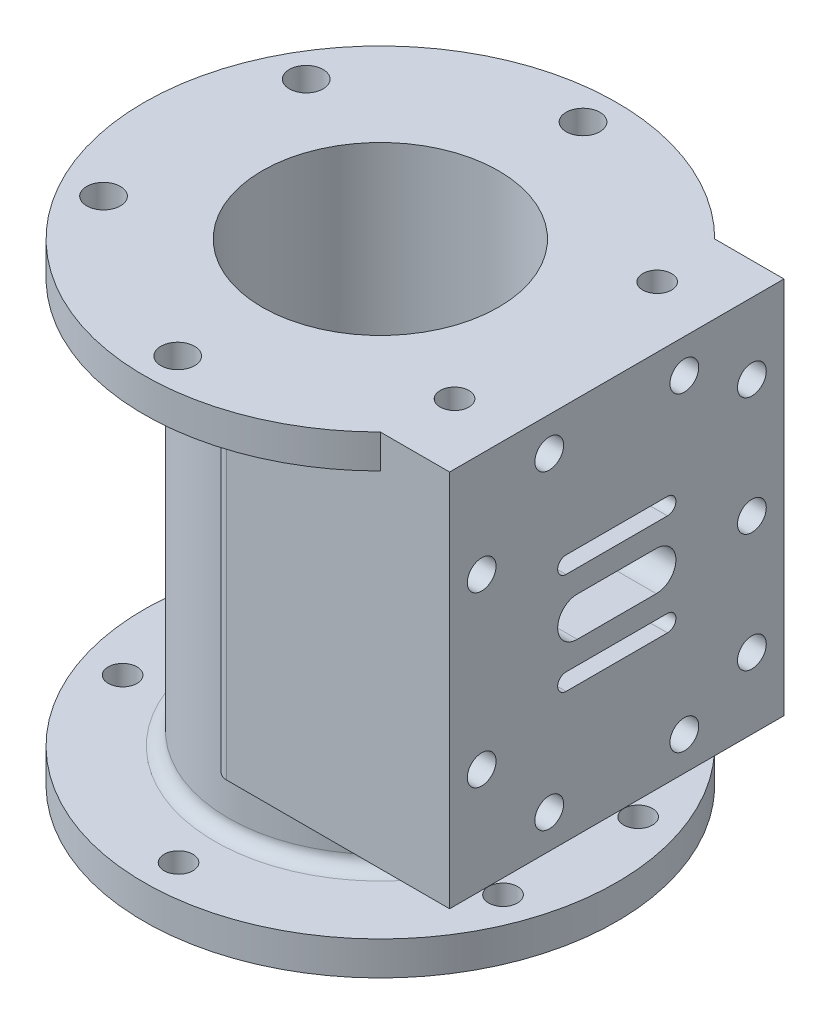
SolidWorks part; units mm, degrees
ref_plane "Front Plane" through (0, 0, 0) normal (0, 0, 1) x (1, 0, 0)
ref_plane "Top Plane" through (0, 0, 0) normal (0, 1, 0) x (1, 0, 0)
ref_plane "Right Plane" through (0, 0, 0) normal (1, 0, 0) x (0, 0, -1)
sketch "Sketch2" plane through (0, 0, 0) normal (0, 0, 1) x (1, 0, 0)
  line L0 (0, -56.0843) -> (0, 32.8157) construction
  line L1 (-22.225, 38.5088) -> (-44.45, 38.5088)
  line L2 (-44.45, 38.5088) -> (-44.45, 32.1588)
  line L3 (-44.45, 32.1588) -> (-28.575, 32.1588)
  line L4 (-28.575, 32.1588) -> (-28.575, -44.0412)
  line L5 (-28.575, -44.0412) -> (-44.45, -44.0412)
  line L6 (-44.45, -44.0412) -> (-44.45, -50.3912)
  line L7 (-44.45, -50.3912) -> (-22.225, -50.3912)
  line L8 (-22.225, -50.3912) -> (-22.225, 26.4657)
  line L9 (-22.225, 26.4657) -> (-22.225, 38.5088)
  dimension "D1" = 88.9
  dimension "D2" = 6.35
  dimension "D3" = 44.45
  dimension "D4" = 57.15
  dimension "D5" = 88.9
  dimension "D6" = 88.9
  dimension "D7" = 6.35
revolve "Revolve1" add sketch "Sketch2" angle 360 about L0
ref_plane "Plane1" through (44.45, 0, 0) normal (1, 0, 0) x (0, 0, -1)
sketch "Sketch3" plane through (44.45, 0, 0) normal (1, 0, 0) x (0, 0, -1)
  line L0 (31.4325, 38.5088) -> (-31.4325, 38.5088)
  line L1 (22.225, 38.5088) -> (-22.225, 38.5088) construction
  line L2 (44.45, 38.5088) -> (-44.45, 38.5088) construction
  line L3 (-31.4325, 38.5088) -> (-31.4325, -32.6112)
  line L4 (-31.4325, -32.6112) -> (31.4325, -32.6112)
  line L5 (0, -32.6112) -> (0, 38.5088) construction
  line L6 (31.4325, 38.5088) -> (31.4325, -32.6112)
  line L7 (-7.4295, 2.9488) -> (7.4295, 2.9488) construction
  line L8 (-7.4295, 6.6318) -> (7.4295, 6.6318)
  line L9 (-7.4295, -0.7342) -> (7.4295, -0.7342)
  line L10 (-9.525, 12.4738) -> (9.525, 12.4738) construction
  line L11 (-9.525, 14.0613) -> (9.525, 14.0613)
  line L12 (-9.525, 10.8863) -> (9.525, 10.8863)
  line L13 (0, 2.9488) -> (27.4597, 2.9488) construction
  line L14 (-9.525, -6.5762) -> (9.525, -6.5762) construction
  line L15 (-9.525, -8.1637) -> (9.525, -8.1637)
  line L16 (-9.525, -4.9887) -> (9.525, -4.9887)
  line L17 (25.4, 25.1738) -> (25.4, -19.2762) construction
  line L18 (-17.7165, 24.7928) -> (17.7165, 24.7928) construction
  line L19 (-17.7165, 24.7928) -> (-17.7165, -18.8952) construction
  line L20 (-17.7165, -18.8952) -> (17.7165, -18.8952) construction
  line L21 (17.7165, 24.7928) -> (17.7165, -18.8952) construction
  line L22 (-17.7165, 24.7928) -> (17.7165, -18.8952) construction
  line L23 (-17.7165, -18.8952) -> (17.7165, 24.7928) construction
  arc A0 (-7.4295, 6.6318) -> (-7.4295, -0.7342) centre (-7.4295, 2.9488) ccw
  arc A1 (7.4295, -0.7342) -> (7.4295, 6.6318) centre (7.4295, 2.9488) ccw
  arc A2 (-9.525, 14.0613) -> (-9.525, 10.8863) centre (-9.525, 12.4738) ccw
  arc A3 (9.525, 10.8863) -> (9.525, 14.0613) centre (9.525, 12.4738) ccw
  arc A4 (-9.525, -8.1637) -> (-9.525, -4.9887) centre (-9.525, -6.5762) cw
  arc A5 (9.525, -4.9887) -> (9.525, -8.1637) centre (9.525, -6.5762) cw
  circle A6 centre (12.7, 32.1588) radius 3.175
  circle A7 centre (25.4, 25.1738) radius 3.175
  circle A8 centre (-12.7, 32.1588) radius 3.175
  circle A9 centre (-25.4, 25.1738) radius 3.175
  circle A10 centre (25.4, -19.2762) radius 3.175
  circle A11 centre (12.7, -26.2612) radius 3.175
  circle A12 centre (-12.7, -26.2612) radius 3.175
  circle A13 centre (-25.4, -19.2762) radius 3.175
  circle A14 centre (25.4, 2.9488) radius 3.175
  point P12 (0, 2.9488)
  point P17 (-11.1125, 2.9488)
  point P18 (11.1125, 2.9488)
  point P21 (0, 12.4738)
  point P26 (-11.1125, 12.4738)
  point P27 (11.1125, 12.4738)
  point P32 (0, -6.5762)
  dimension "D8" = 13.716
  dimension "D1" = 62.865
  dimension "D2" = 71.12
  dimension "D3" = 22.225
  dimension "D4" = 7.366
  dimension "D5" = 22.225
  dimension "D6" = 3.175
  dimension "D7" = 9.525
  dimension "D9" = 29.21
  dimension "D10" = 25.4
sketch "Sketch5" plane through (0, 38.5088, 0) normal (0, 1, 0) x (1, 0, 0)
  line L0 (-38.1, 0) -> (38.1, 0) construction
  line L1 (0, 0) -> (0, 38.1) construction
  circle A0 centre (0, 0) radius 38.1 construction
  circle A1 centre (0, 38.1) radius 3.175
  circle A2 centre (32.9956, 19.05) radius 3.175
  circle A3 centre (32.9956, -19.05) radius 3.175
  circle A4 centre (0, -38.1) radius 3.175
  circle A5 centre (-32.9956, -19.05) radius 3.175
  circle A6 centre (-32.9956, 19.05) radius 3.175
  point P20 (0, 0)
  dimension "D1" = 6
extrude "Cut-Extrude1" cut sketch "Sketch5" against normal up to next
sketch "Sketch6" plane through (0, -50.3912, 0) normal (0, -1, 0) x (1, 0, 0)
  line L0 (48.895, 0) -> (-48.895, 0) construction
  circle A0 centre (0, 0) radius 37.9491 construction
  circle A1 centre (0, 37.9491) radius 3.175
  circle A2 centre (0, -37.9491) radius 3.175
  circle A3 centre (35.7609, -12.7) radius 3.175
  circle A4 centre (-35.7609, -12.7) radius 3.175
  circle A5 centre (35.7609, 12.7) radius 3.175
  circle A6 centre (-35.7609, 12.7) radius 3.175
  dimension "D1" = 12.7
  dimension "D2" = 12.7
extrude "Boss-Extrude3" add sketch "Sketch3" against normal up to surface (44.45 mm away) contours L3 L4 L6 L0 up to plane "Right Plane"
sketch "Sketch8" plane through (0, 38.5088, 0) normal (0, 1, 0) x (1, 0, 0)
  circle A0 centre (0, 0) radius 22.225
extrude "Cut-Extrude3" cut sketch "Sketch8" against normal through all
sketch "Sketch10" plane through (0, 38.5088, 0) normal (0, 1, 0) x (1, 0, 0)
  circle A0 centre (0, 0) radius 38.1 construction
  circle A1 centre (0, 38.1) radius 3.175 construction
  circle A2 centre (0, 38.1) radius 3.175 construction
  circle A3 centre (32.9956, 19.05) radius 3.175
  circle A4 centre (32.9956, -19.05) radius 3.175
  circle A5 centre (0, -38.1) radius 3.175 construction
  circle A6 centre (-32.9956, -19.05) radius 3.175 construction
  circle A7 centre (-32.9956, 19.05) radius 3.175 construction
  point P20 (0, 0)
  dimension "D1" = 6
sketch "Sketch11" plane through (44.45, 0, 0) normal (1, 0, 0) x (0, 0, -1)
  circle A1 centre (-25.4, 25.1738) radius 3.175
  circle A10 centre (-25.4, 25.1738) radius 3.175
  circle A11 centre (-12.7, 32.1588) radius 3.175
  circle A12 centre (-12.7, 32.1588) radius 3.175
  circle A13 centre (12.7, 32.1588) radius 3.175
  circle A14 centre (12.7, 32.1588) radius 3.175
  circle A15 centre (25.4, 2.9488) radius 3.175
  circle A20 centre (25.4, 2.9488) radius 3.175
  circle A21 centre (-25.4, -19.2762) radius 3.175
  circle A22 centre (-25.4, -19.2762) radius 3.175
  circle A23 centre (-12.7, -26.2612) radius 3.175
  circle A24 centre (-12.7, -26.2612) radius 3.175
  circle A25 centre (12.7, -26.2612) radius 3.175
  circle A26 centre (12.7, -26.2612) radius 3.175
  circle A27 centre (25.4, -19.2762) radius 3.175
  circle A28 centre (25.4, -19.2762) radius 3.175
  circle A29 centre (25.4, 25.1738) radius 3.175
  circle A30 centre (25.4, 25.1738) radius 3.175
  dimension "D4" = 0
  dimension "D5" = 0
  dimension "D6" = 0
  dimension "D8" = 0
  dimension "D9" = 0
  dimension "D10" = 0
  dimension "D11" = 0
  dimension "D12" = 0
  dimension "D13" = 0
fillet "Fillet1" radius 2.54 2 edges at (0, -0.2262, -31.4325) (0, -0.2262, 31.4325)
fillet "Fillet2" radius 2.54 2 edges at (-28.575, 32.1588, 0) (0, -44.0412, -28.575)
sketch "Sketch13" plane through (44.45, 0, 0) normal (1, 0, 0) x (0, 0, -1)
  line L2 (9.525, 14.0613) -> (-9.525, 14.0613)
  line L3 (-9.525, 10.8863) -> (9.525, 10.8863)
  line L12 (9.525, 14.0613) -> (-9.525, 14.0613)
  line L13 (-9.525, 10.8863) -> (9.525, 10.8863)
  line L14 (7.4295, 6.6318) -> (-7.4295, 6.6318)
  line L15 (-7.4295, -0.7342) -> (7.4295, -0.7342)
  line L16 (7.4295, 6.6318) -> (-7.4295, 6.6318)
  line L17 (-7.4295, -0.7342) -> (7.4295, -0.7342)
  line L18 (-9.525, -8.1637) -> (9.525, -8.1637)
  line L19 (9.525, -4.9887) -> (-9.525, -4.9887)
  line L20 (-9.525, -8.1637) -> (9.525, -8.1637)
  line L21 (9.525, -4.9887) -> (-9.525, -4.9887)
  arc A2 (9.525, 10.8863) -> (9.525, 14.0613) centre (9.525, 12.4738) ccw
  arc A3 (-9.525, 14.0613) -> (-9.525, 10.8863) centre (-9.525, 12.4738) ccw
  arc A4 (9.525, 10.8863) -> (9.525, 14.0613) centre (9.525, 12.4738) ccw
  arc A5 (-9.525, 14.0613) -> (-9.525, 10.8863) centre (-9.525, 12.4738) ccw
  arc A6 (7.4295, -0.7342) -> (7.4295, 6.6318) centre (7.4295, 2.9488) ccw
  arc A7 (-7.4295, 6.6318) -> (-7.4295, -0.7342) centre (-7.4295, 2.9488) ccw
  arc A8 (7.4295, -0.7342) -> (7.4295, 6.6318) centre (7.4295, 2.9488) ccw
  arc A9 (-7.4295, 6.6318) -> (-7.4295, -0.7342) centre (-7.4295, 2.9488) ccw
  arc A16 (9.525, -8.1637) -> (9.525, -4.9887) centre (9.525, -6.5762) ccw
  arc A17 (-9.525, -4.9887) -> (-9.525, -8.1637) centre (-9.525, -6.5762) ccw
  arc A18 (9.525, -8.1637) -> (9.525, -4.9887) centre (9.525, -6.5762) ccw
  arc A19 (-9.525, -4.9887) -> (-9.525, -8.1637) centre (-9.525, -6.5762) ccw
  dimension "D2" = 0
  dimension "D3" = 0
  dimension "D7" = 0
sketch "Sketch18" plane through (44.45, 0, 0) normal (1, 0, 0) x (0, 0, -1)
  point P0 (-25.4, 25.1738)
  point P1 (-12.7, 32.1588)
  point P3 (12.7, 32.1588)
  point P5 (25.4, 25.1738)
  point P7 (25.4, 2.9488)
  point P9 (25.4, -19.2762)
  point P11 (12.7, -26.2612)
  point P13 (-12.7, -26.2612)
  point P15 (-25.4, -19.2762)
  point P17 (-25.4, 25.1738)
hole_wizard "1/4-28 Tapped Hole1" positions "3DSketch3" profile "Sketch19" tap size "1/4-28" standard "ANSI Inch"
sketch3d "3DSketch3"
  point P3 (44.45, 32.1588, 12.7)
  point P6 (44.45, 32.1588, -12.7)
  point P9 (44.45, 25.1738, -25.4)
  point P12 (44.45, 2.9488, -25.4)
  point P15 (44.45, -19.2762, -25.4)
  point P18 (44.45, -26.2612, -12.7)
  point P21 (44.45, -26.2612, 12.7)
sketch "Sketch19" plane through (44.45, 32.1588, 12.7) normal (0, 1, 0) x (0, 0, -1)
  line L0 (0, 0) -> (0, 14.3254)
  line L1 (0, 14.3254) -> (2.7051, 12.7)
  line L2 (2.7051, 12.7) -> (2.7051, 0)
  line L5 (2.7051, 0) -> (0, 0)
  line L10 (0, 14.3254) -> (-2.7051, 12.7) construction
  line L11 (0, -6.35) -> (0, 107.95) construction
  dimension "Tap Drill Dia." = 5.4102
  dimension "Tap Drill Depth" = 12.7
  dimension "Drill Angle" = 118
cosmetic thread "Hole Thread2" parameters "D1"=12.7, "D2"=6.35
cosmetic thread "Hole Thread3" parameters "D1"=12.7, "D2"=6.35
cosmetic thread "Hole Thread4" parameters "D1"=12.7, "D2"=6.35
cosmetic thread "Hole Thread5" parameters "D1"=12.7, "D2"=6.35
cosmetic thread "Hole Thread6" parameters "D1"=12.7, "D2"=6.35
cosmetic thread "Hole Thread7" parameters "D1"=12.7, "D2"=6.35
cosmetic thread "Hole Thread8" parameters "D1"=12.7, "D2"=6.35
hole_wizard "1/4-28 Tapped Hole7" positions "3DSketch4" profile "Sketch20" tap size "1/4-28" standard "ANSI Inch" end condition up to next
sketch3d "3DSketch4"
  point P0 (0, -50.3912, -37.9491)
  point P4 (35.7609, -50.3912, -12.7)
  point P7 (35.7609, -50.3912, 12.7)
  point P10 (-35.7609, -50.3912, -12.7)
  point P13 (-35.7609, -50.3912, 12.7)
  point P16 (0, -50.3912, 37.9491)
sketch "Sketch20" plane through (0, -50.3912, -37.9491) normal (1, 0, 0) x (0, 0, -1)
  line L0 (0, 0) -> (0, 6.35)
  line L1 (0, 6.35) -> (2.7051, 6.35)
  line L2 (2.7051, 6.35) -> (2.7051, 0)
  line L5 (2.7051, 0) -> (0, 0)
  line L11 (0, -6.35) -> (0, 107.95) construction
  dimension "Thru Tap Drill Dia." = 5.4102
  dimension "Thru Tap Drill Depth" = 6.35
cosmetic thread "Hole Thread10" parameters "D2"=6.35
cosmetic thread "Hole Thread11" parameters "D2"=6.35
cosmetic thread "Hole Thread12" parameters "D2"=6.35
cosmetic thread "Hole Thread13" parameters "D2"=6.35
cosmetic thread "Hole Thread14" parameters "D2"=6.35
cosmetic thread "Hole Thread15" parameters "D2"=6.35
hole_wizard "1/4-28 Tapped Hole8" positions "3DSketch5" profile "Sketch21" tap size "1/4-28" standard "ANSI Inch"
sketch3d "3DSketch5"
  point P0 (32.9956, 38.5088, -19.05)
  point P3 (32.9956, 38.5088, 19.05)
sketch "Sketch21" plane through (32.9956, 38.5088, -19.05) normal (1, 0, 0) x (0, 0, 1)
  line L0 (0, 0) -> (0, 14.3254)
  line L1 (0, 14.3254) -> (2.7051, 12.7)
  line L2 (2.7051, 12.7) -> (2.7051, 0)
  line L5 (2.7051, 0) -> (0, 0)
  line L10 (0, 14.3254) -> (-2.7051, 12.7) construction
  line L11 (0, -6.35) -> (0, 107.95) construction
  dimension "Tap Drill Dia." = 5.4102
  dimension "Tap Drill Depth" = 12.7
  dimension "Drill Angle" = 118
cosmetic thread "Hole Thread16" parameters "D1"=12.7, "D2"=6.35
cosmetic thread "Hole Thread17" parameters "D1"=12.7, "D2"=6.35
extrude "Cut-Extrude4" cut sketch "Sketch13" against normal blind 11.43
sketch "Sketch22" plane through (0, 0, 0) normal (0, 0, 1) x (1, 0, 0)
  line L0 (33.02, 14.0613) -> (22.1189, 33.487)
  line L1 (33.02, 14.0613) -> (44.45, 14.0613) construction
  line L2 (22.1189, 33.487) -> (22.1189, 36.6437)
  line L3 (22.1189, 36.6437) -> (34.7914, 14.0613)
  line L4 (34.7914, 14.0613) -> (33.02, 14.0613)
  line L5 (33.02, -8.1637) -> (22.1189, -46.8494)
  line L6 (22.1189, -46.8494) -> (22.1189, -51.2304)
  line L7 (22.1189, -51.2304) -> (34.2545, -8.1637)
  line L8 (33.02, -8.1637) -> (44.45, -8.1637) construction
  line L9 (34.2545, -8.1637) -> (33.02, -8.1637)
extrude "Cut-Extrude6" cut sketch "Sketch22" against normal up to vertex (9.525 mm away) and the other way up to vertex (9.525 mm away) up to point (33.02, 10.8863, -9.525) other way up to point (33.02, -8.1637, 9.525)
ref_plane "Plane2" through (0, 2.9488, 0) normal (0, 1, 0) x (1, 0, 0)
hole_wizard "1/4-28 Tapped Hole9" positions "3DSketch6" profile "Sketch23" tap size "1/4-28" standard "ANSI Inch"
sketch3d "3DSketch6"
  point P0 (44.45, -12.9262, 25.4)
  point P5 (44.45, 18.8238, 25.4)
  dimension "D1" = 15.875
  dimension "D2" = 15.875
  dimension "D3" = 6.0325
  dimension "D4" = 6.0325
sketch "Sketch23" plane through (44.45, -12.9262, 25.4) normal (0, 1, 0) x (0, 0, -1)
  line L0 (0, 0) -> (0, 14.3254)
  line L1 (0, 14.3254) -> (2.7051, 12.7)
  line L2 (2.7051, 12.7) -> (2.7051, 0)
  line L5 (2.7051, 0) -> (0, 0)
  line L10 (0, 14.3254) -> (-2.7051, 12.7) construction
  line L11 (0, -6.35) -> (0, 107.95) construction
  dimension "Tap Drill Dia." = 5.4102
  dimension "Tap Drill Depth" = 12.7
  dimension "Drill Angle" = 118
cosmetic thread "Hole Thread18" parameters "D1"=12.7, "D2"=6.35
cosmetic thread "Hole Thread19" parameters "D1"=12.7, "D2"=6.35
ref_plane "Plane3" through (0, 0, 31.4325) normal (0, 0, 1) x (1, 0, 0)
